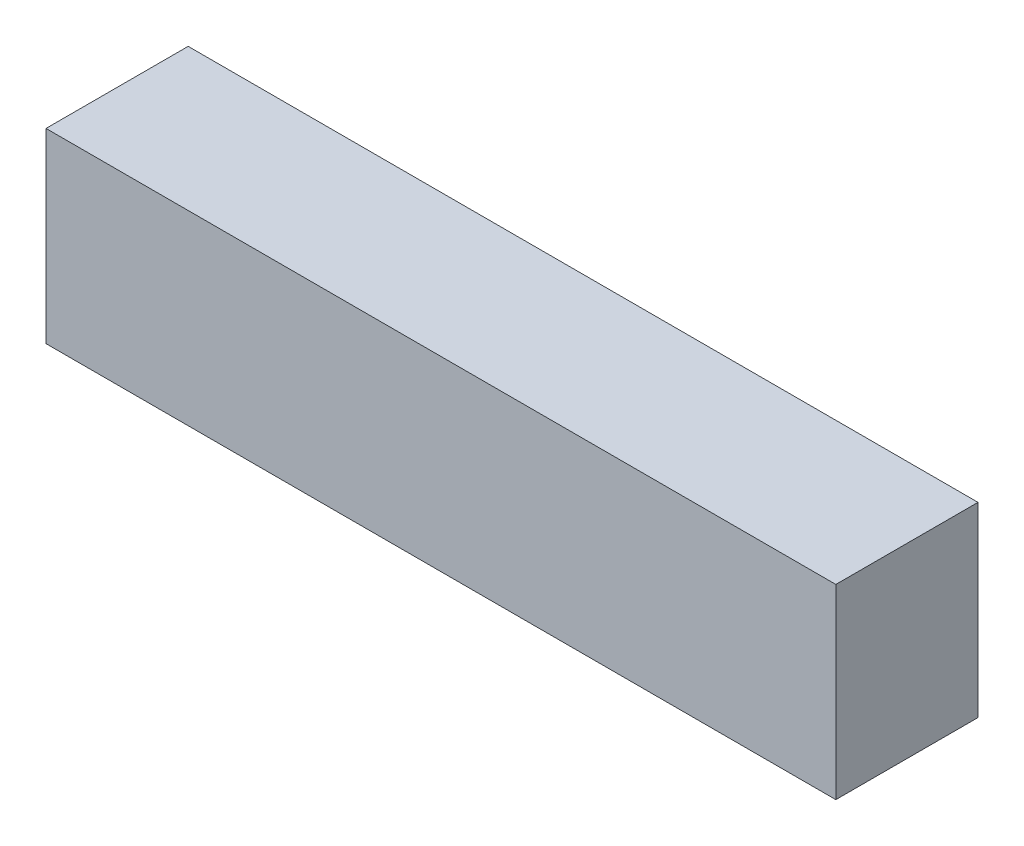
SolidWorks part; units mm, degrees
ref_plane "Front Plane" through (0, 0, 0) normal (0, 0, 1) x (1, 0, 0)
ref_plane "Top Plane" through (0, 0, 0) normal (0, 1, 0) x (1, 0, 0)
ref_plane "Right Plane" through (0, 0, 0) normal (1, 0, 0) x (0, 0, -1)
sketch "Sketch1" plane through (0, 0, 0) normal (0, 0, 1) x (1, 0, 0)
  line L1 (-83.9447, -6.3134) -> (-20.4447, -6.3134)
  line L2 (-83.9447, -6.3134) -> (-83.9447, -21.2994)
  line L3 (-83.9447, -21.2994) -> (-20.4447, -21.2994)
  line L4 (-20.4447, -6.3134) -> (-20.4447, -21.2994)
  dimension "D1" = 63.5
  dimension "D2" = 14.986
extrude "Boss-Extrude1" add sketch "Sketch1" along normal blind 11.43 contours L2 L1 L4 L3
